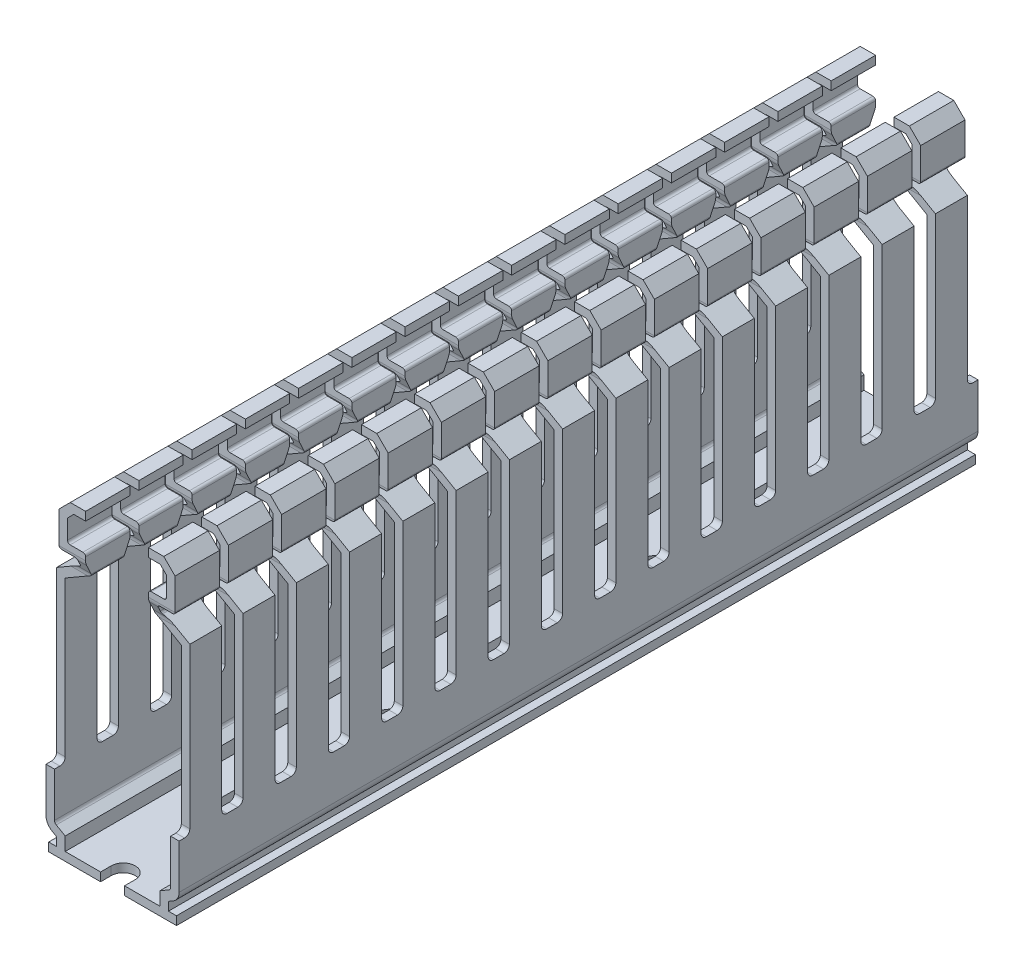
SolidWorks part; units mm, degrees
material "ABS"
ref_plane "Front Plane" through (0, 0, 0) normal (0, 0, 1) x (1, 0, 0)
ref_plane "Top Plane" through (0, 0, 0) normal (0, 1, 0) x (1, 0, 0)
ref_plane "Right Plane" through (0, 0, 0) normal (1, 0, 0) x (0, 0, -1)
sketch "Sketch1" plane through (0, 0, 0) normal (0, 0, 1) x (1, 0, 0)
  line L0 (0, 29) -> (0, -29) construction
  line L1 (12.5, -29) -> (-12.5, -29) construction
  line L2 (12.5, -29) -> (12.5, 29) construction
  line L3 (12.5, 29) -> (-12.5, 29) construction
  line L4 (-12.5, -29) -> (-12.5, 29) construction
  line L5 (12.5, -29) -> (-12.5, 29) construction
  line L6 (12.5, 29) -> (-12.5, -29) construction
  line L7 (-12.5, -23.3359) -> (-12.5, 16)
  line L8 (-12, -27.4) -> (-12, -29)
  line L9 (-12.5, -27.4) -> (-10.5, -27.4) construction
  line L10 (-10.5, -27.4) -> (-10.5, -25.8)
  line L11 (-10.5, -25.8) -> (-11.366, -25.3)
  line L12 (-12, -29) -> (12, -29)
  line L13 (-12.5, 16) -> (-7.75, 18.7424)
  line L14 (8.9, -27.4) -> (-8.9, -27.4)
  line L15 (-8.9, -27.4) -> (-8.9, -24.8762)
  line L16 (-8.9, -24.8762) -> (-10.566, -23.9144)
  line L17 (-9.7, -24.4144) -> (-10.566, -23.9144) construction
  line L18 (-10.9, -23.3359) -> (-10.9, 15.0762)
  line L19 (-10.9, 21) -> (-10.9, 26.8787)
  line L20 (-12, -27.4) -> (-10.5, -27.4)
  line L21 (-7.5, 19.1754) -> (-7.5, 20)
  line L22 (-8, 20.5) -> (-10.4, 20.5)
  line L23 (-10.9, 26.8787) -> (-8.7787, 29)
  line L24 (-8.7787, 29) -> (-5.9, 29)
  line L25 (-5.9, 29) -> (-5.9, 27.4)
  line L26 (-5.9, 27.4) -> (-8.1159, 27.4)
  line L27 (-8.1159, 27.4) -> (-9.3, 26.2159)
  line L28 (-9.3, 26.2159) -> (-9.3, 22.6)
  line L29 (-8.8, 22.1) -> (-6.4, 22.1)
  line L30 (-5.9, 21.6) -> (-5.9, 18.2517)
  line L31 (-6.15, 17.8187) -> (-10.9, 15.0762)
  line L32 (12, -27.4) -> (12, -29)
  line L33 (12, -27.4) -> (10.5, -27.4)
  line L34 (10.5, -27.4) -> (10.5, -25.8)
  line L35 (8.9, -27.4) -> (8.9, -24.8762)
  line L36 (10.5, -25.8) -> (11.366, -25.3)
  line L37 (8.9, -24.8762) -> (10.566, -23.9144)
  line L38 (10.9, -23.3359) -> (10.9, 15.0762)
  line L39 (12.5, -23.3359) -> (12.5, 16)
  line L40 (6.15, 17.8187) -> (10.9, 15.0762)
  line L41 (12.5, 16) -> (7.75, 18.7424)
  line L42 (7.5, 19.1754) -> (7.5, 20)
  line L43 (5.9, 21.6) -> (5.9, 18.2517)
  line L44 (8, 20.5) -> (10.4, 20.5)
  line L45 (8.8, 22.1) -> (6.4, 22.1)
  line L46 (9.3, 26.2159) -> (9.3, 22.6)
  line L47 (10.9, 21) -> (10.9, 26.8787)
  line L48 (8.1159, 27.4) -> (9.3, 26.2159)
  line L49 (10.9, 26.8787) -> (8.7787, 29)
  line L50 (5.9, 27.4) -> (8.1159, 27.4)
  line L51 (5.9, 29) -> (5.9, 27.4)
  line L52 (8.7787, 29) -> (5.9, 29)
  arc A0 (-11.366, -25.3) -> (-12.5, -23.3359) centre (-10.2321, -23.3359) cw
  arc A1 (-10.566, -23.9144) -> (-10.9, -23.3359) centre (-10.2321, -23.3359) cw
  arc A2 (-10.566, -23.9144) -> (-10.9, -23.3359) centre (-10.2321, -23.3359) cw construction
  arc A3 (11.366, -25.3) -> (12.5, -23.3359) centre (10.2321, -23.3359) ccw
  arc A4 (10.566, -23.9144) -> (10.9, -23.3359) centre (10.2321, -23.3359) ccw
  arc A5 (8.8, 22.1) -> (9.3, 22.6) centre (8.8, 22.6) ccw
  arc A6 (10.4, 20.5) -> (10.9, 21) centre (10.4, 21) ccw
  arc A7 (7.75, 18.7424) -> (7.5, 19.1754) centre (8, 19.1754) cw
  arc A8 (7.5, 20) -> (8, 20.5) centre (8, 20) cw
  arc A9 (6.15, 17.8187) -> (5.9, 18.2517) centre (6.4, 18.2517) cw
  arc A10 (5.9, 21.6) -> (6.4, 22.1) centre (6.4, 21.6) cw
  arc A11 (-9.3, 22.6) -> (-8.8, 22.1) centre (-8.8, 22.6) ccw
  arc A12 (-10.4, 20.5) -> (-10.9, 21) centre (-10.4, 21) cw
  arc A13 (-6.4, 22.1) -> (-5.9, 21.6) centre (-6.4, 21.6) cw
  arc A14 (-7.5, 20) -> (-8, 20.5) centre (-8, 20) ccw
  arc A15 (-7.75, 18.7424) -> (-7.5, 19.1754) centre (-8, 19.1754) ccw
  arc A16 (-5.9, 18.2517) -> (-6.15, 17.8187) centre (-6.4, 18.2517) cw
  point P0 (0, 0)
  point P40 (0, -27.4)
  point P66 (9.3, 22.1)
  point P69 (10.9, 20.5)
  point P72 (7.5, 18.8868)
  point P75 (7.5, 20.5)
  point P78 (5.9, 17.963)
  point P81 (5.9, 22.1)
  point P84 (-9.3, 22.1)
  point P87 (-10.9, 20.5)
  point P90 (-5.9, 22.1)
  point P93 (-7.5, 20.5)
  point P96 (-7.5, 18.8868)
  point P99 (-5.9, 17.963)
  dimension "D13" = 0.5
  dimension "D1" = 58
  dimension "D2" = 25
  dimension "D3" = 120
  dimension "D4" = 2
  dimension "D5" = 5
  dimension "delta" = 1.6
  dimension "D6" = 3
  dimension "D7" = 1
  dimension "D8" = 225
  dimension "D10" = 0.5
  dimension "D11" = 45
  dimension "D12" = 4.5
  dimension "D17" = 1.6
  dimension "D9" = 120
extrude "Boss-Extrude1" add sketch "Sketch1" against normal blind 150
sketch "Sketch4" plane through (0, 0, 0) normal (0, 0, 1) x (1, 0, 0)
  line L0 (0, 31) -> (0, -32.4953) construction
  line L1 (11, 31) -> (-11, 31)
  line L2 (-13, 29) -> (-13, 17.5)
  line L3 (-13, 17.5) -> (-14, 16.9226)
  line L4 (-14, 16.9226) -> (-13.5, 16.0566)
  line L5 (-13.5, 16.0566) -> (-8.4689, 18.9613)
  line L6 (-8.4689, 18.9613) -> (-8.9689, 19.8274)
  line L7 (-8.9689, 19.8274) -> (-12, 18.0774)
  line L8 (-12, 18.0774) -> (-12, 28)
  line L9 (-10, 30) -> (10, 30)
  line L10 (-12, -29) -> (12, -29) construction
  line L11 (8.4689, 18.9613) -> (8.9689, 19.8274)
  line L12 (8.9689, 19.8274) -> (12, 18.0774)
  line L13 (12, 18.0774) -> (12, 28)
  line L14 (13, 29) -> (13, 17.5)
  line L15 (13, 17.5) -> (14, 16.9226)
  line L16 (14, 16.9226) -> (13.5, 16.0566)
  line L17 (13.5, 16.0566) -> (8.4689, 18.9613)
  arc A0 (-11, 31) -> (-13, 29) centre (-11, 29) ccw
  arc A1 (-12, 28) -> (-10, 30) centre (-10, 28) cw
  arc A2 (12, 28) -> (10, 30) centre (10, 28) ccw
  arc A3 (11, 31) -> (13, 29) centre (11, 29) cw
  point P20 (0, 30)
  dimension "D7" = 2
  dimension "D1" = 60
  dimension "D2" = 120
  dimension "D3" = 1
  dimension "D4" = 1
  dimension "D5" = 1
  dimension "D6" = 13
  dimension "D8" = 13.5
  dimension "D9" = 14
  dimension "D10" = 3.5
extrude "Boss-Extrude2" [suppressed] add sketch "Sketch4" against normal blind 150 separate body
sketch "Sketch2" plane through (0, 0, 0) normal (1, 0, 0) x (0, 0, -1)
  line L0 (150, -29) -> (0, -29) construction
  line L1 (-1, -15) -> (1, -15)
  line L2 (-2, -14) -> (-2, 17.5566)
  line L3 (-2, 18) -> (2, 18) construction
  line L4 (2, -14) -> (2, 17.5566)
  line L6 (-1.8126, 18.4018) -> (-1.0216, 20.0982)
  line L7 (150, 20.5) -> (0, 20.5) construction
  line L8 (1.8126, 18.4018) -> (1.0216, 20.0982)
  line L9 (150, 20.5) -> (0, 20.5) construction
  line L10 (0.8342, 20.9434) -> (0.8342, 30.5)
  line L11 (0.8342, 30.5) -> (-0.8342, 30.5)
  line L12 (-0.8342, 30.5) -> (-0.8342, 20.9434)
  line L13 (0, -23.3359) -> (0, 16) construction
  arc A0 (1, -15) -> (2, -14) centre (1, -14) ccw
  arc A1 (-1, -15) -> (-2, -14) centre (-1, -14) cw
  arc A2 (1.8126, 18.4018) -> (2, 17.5566) centre (0, 17.5566) cw
  arc A3 (1.0216, 20.0982) -> (0.8342, 20.9434) centre (2.8342, 20.9434) cw
  arc A4 (-2, 17.5566) -> (-1.8126, 18.4018) centre (0, 17.5566) cw
  arc A5 (-1.0216, 20.0982) -> (-0.8342, 20.9434) centre (-2.8342, 20.9434) ccw
  point P12 (-2, -15)
  point P26 (0.8342, 20.5)
  point P32 (-0.8342, 20.5)
  dimension "D5" = 1
  dimension "D9" = 2
  dimension "D1" = 14
  dimension "D2" = 4
  dimension "D3" = 2
  dimension "D4" = 33
  dimension "D6" = 205
  dimension "D7" = 205
  dimension "D8" = 10
extrude "Cut-Extrude1" cut sketch "Sketch2" against normal mid plane 30
pattern_linear "LPattern1" count 16 spacing 10 along (0, 0, -1) of "Cut-Extrude1"
sketch "Sketch3" plane through (0, -29, 0) normal (0, -1, 0) x (1, 0, 0)
  line L0 (0, 2) -> (0, -2) construction
  line L1 (2.25, 2) -> (2.25, -2)
  line L2 (-2.25, 2) -> (-2.25, -2)
  line L3 (0, -21) -> (0, -29) construction
  line L4 (3, -21) -> (3, -29)
  line L5 (-3, -21) -> (-3, -29)
  arc A0 (2.25, 2) -> (-2.25, 2) centre (0, 2) ccw
  arc A1 (-2.25, -2) -> (2.25, -2) centre (0, -2) ccw
  arc A2 (3, -21) -> (-3, -21) centre (0, -21) ccw
  arc A3 (-3, -29) -> (3, -29) centre (0, -29) ccw
  point P2 (0, 0)
  point P10 (0, -25)
  dimension "D1" = 4.5
  dimension "D2" = 4
  dimension "D3" = 25
  dimension "D4" = 8
  dimension "D5" = 6
extrude "Cut-Extrude2" cut sketch "Sketch3" against normal blind 30
pattern_linear "LPattern2" count 4 spacing 50 along (0, 0, -1) of "Cut-Extrude2"
equation "\"delta\"=\"D17@Sketch1\""
equation "\"D1@LPattern1\" = (\"D1@Boss-Extrude1\"/10)+1"
equation "\"D1@LPattern2\" = (\"D1@Boss-Extrude1\"/50)+1"
equation "\"D1@Boss-Extrude2\" = \"D1@Boss-Extrude1\""
